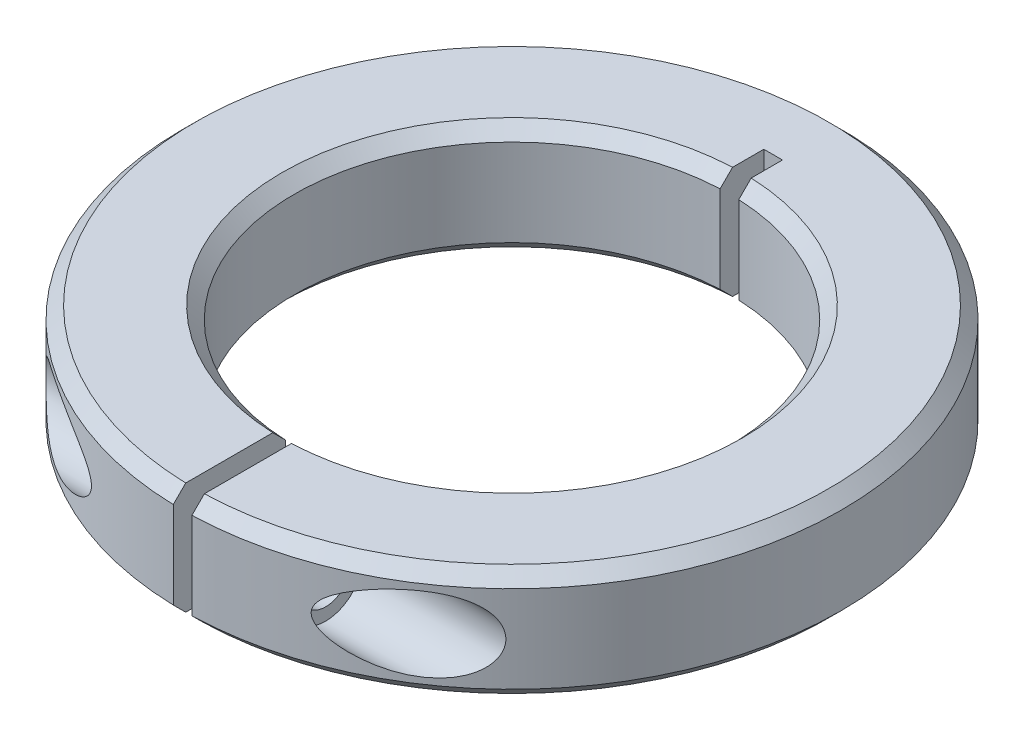
SolidWorks part; units mm, degrees
ref_plane "Front Plane" through (0, 0, 0) normal (0, 0, 1) x (1, 0, 0)
ref_plane "Top Plane" through (0, 0, 0) normal (0, 1, 0) x (1, 0, 0)
ref_plane "Right Plane" through (0, 0, 0) normal (1, 0, 0) x (0, 0, -1)
sketch "Sketch1" plane through (0, 0, 0) normal (0, 1, 0) x (1, 0, 0)
  line L0 (-0.75, 21) -> (-0.75, 17.4839)
  line L1 (0.75, 21) -> (0.75, 17.4839)
  line L2 (0, 3.9874) -> (0, -3.5975) construction
  line L3 (0.75, 21) -> (-0.75, 21)
  line L4 (-0.75, -17.4839) -> (-0.75, -26.4894)
  line L5 (0.75, -17.4839) -> (0.75, -26.4894)
  arc A0 (0.75, -26.4894) -> (-0.75, -26.4894) centre (0, 0) ccw
  arc A1 (0.75, -17.4839) -> (0.75, 17.4839) centre (0, 0) ccw
  arc A2 (-0.75, 17.4839) -> (-0.75, -17.4839) centre (0, 0) ccw
  point P10 (0.75, -27.5956)
  point P11 (-0.75, -27.5956)
  point P12 (-0.75, -26.4894)
  point P13 (0.75, -26.4894)
  dimension "D3" = 35
  dimension "D4" = 53
  dimension "D1" = 1.5
  dimension "D2" = 21
extrude "Boss-Extrude1" add sketch "Sketch1" along normal blind 9
chamfer "Chamfer1" distance 1 angle 45 6 edges at (17.5, 0, 0) (-17.5, 0, 0) (0, 0, -26.5) (17.5, 9, 0) (-17.5, 9, 0) (0, 9, -26.5)
sketch "Sketch2" plane through (0, 0, 0) normal (1, 0, 0) x (0, 0, -1)
  line L0 (-18.4848, 9) -> (-25.489, 9) construction
  line L1 (-17.4839, 8) -> (-17.4839, 1) construction
  circle A0 centre (-21.9839, 4.5) radius 2
  circle A1 centre (-21.9839, 4.5) radius 3
  point P5 (0, 0)
  point P7 (-20.8101, 4.9112)
  point P8 (-22.982, 3.9269)
  dimension "D1" = 4
  dimension "D2" = 6
  dimension "D3" = 4.5
  dimension "D4" = 4.5
extrude "Cut-Extrude1" cut sketch "Sketch2" against normal mid plane 50 contours A0 region at (0, 4.5, 21.9839)
extrude "Cut-Extrude2" cut sketch "Sketch2<3>" against normal blind 15 from offset 7 contours A1 A0 region at (0, 4.5, 24.8991) offset against normal yes
sketch "Sketch2<3>" plane through (0, 0, 0) normal (1, 0, 0) x (0, 0, -1) same geometry as "Sketch2"
extrude "Cut-Extrude3" cut sketch "Sketch2<4>" along normal blind 17 from offset 7
sketch "Sketch2<4>" plane through (0, 0, 0) normal (1, 0, 0) x (0, 0, -1) same geometry as "Sketch2"
